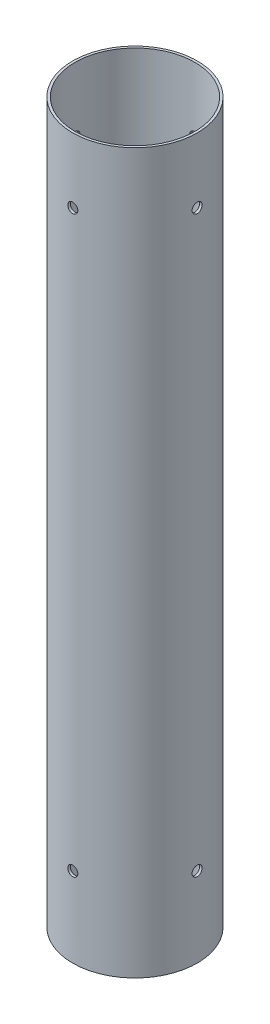
SolidWorks part; units mm, degrees
material "S-Glass Fiber"
ref_plane "Front Plane" through (0, 0, 0) normal (0, 0, 1) x (1, 0, 0)
ref_plane "Top Plane" through (0, 0, 0) normal (0, 1, 0) x (1, 0, 0)
ref_plane "Right Plane" through (0, 0, 0) normal (1, 0, 0) x (0, 0, -1)
sketch "Sketch1" plane through (0, 0, 0) normal (0, 1, 0) x (1, 0, 0)
  circle A0 centre (0, 0) radius 39.624
  circle A1 centre (0, 0) radius 38.1
  dimension "D1" = 79.248
  dimension "D2" = 76.2
extrude "Boss-Extrude1" add sketch "Sketch1" along normal blind 457.2 contours A1 | A0
sketch "Sketch2" plane through (0, 0, 0) normal (0, 0, 1) x (1, 0, 0)
  line L0 (39.624, 457.2) -> (-39.624, 457.2) construction
  circle A0 centre (0, 415.925) radius 3.175
  dimension "D2" = 6.35
  dimension "D1" = 41.275
extrude "Cut-Extrude1" cut sketch "Sketch2" along normal through all
pattern_circular "CirPattern1" count 4 over 360 about axis through (0, 457.2, 0) along (0, -1, 0) of "Cut-Extrude1"
sketch "Sketch4" plane through (0, 0, 0) normal (0, 0, 1) x (1, 0, 0)
  circle A0 centre (0, 50.8) radius 3.175
  point P2 (0, 0)
  point P6 (0, 0)
  dimension "D2" = 6.35
  dimension "D1" = 50.8
extrude "Cut-Extrude2" cut sketch "Sketch4" along normal through all
pattern_circular "CirPattern2" count 4 over 360 about axis through (0, 457.2, 0) along (0, -1, 0) of "Cut-Extrude2" reverse direction yes
